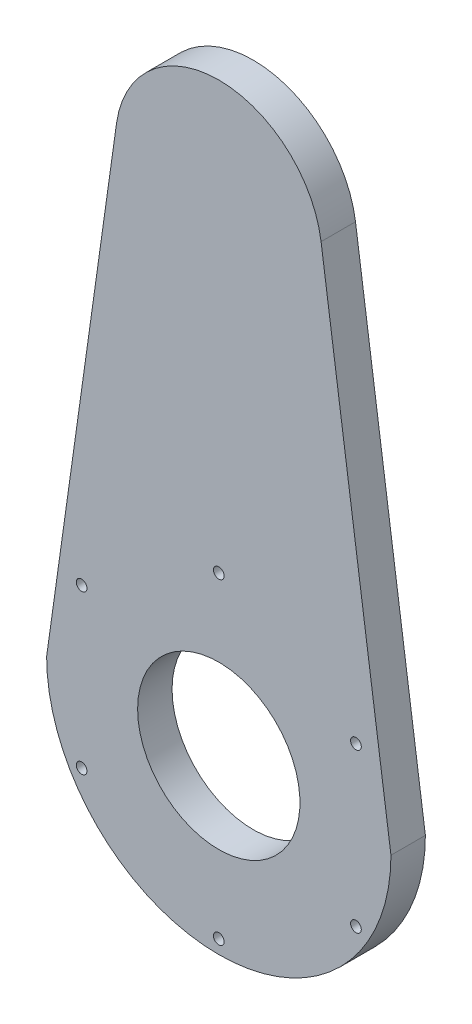
SolidWorks part; units mm, degrees
ref_plane "Ebene vorne" through (0, 0, 0) normal (0, 0, 1) x (1, 0, 0)
ref_plane "Ebene oben" through (0, 0, 0) normal (0, 1, 0) x (1, 0, 0)
ref_plane "Ebene rechts" through (0, 0, 0) normal (1, 0, 0) x (0, 0, -1)
sketch "Skizze1" plane through (0, 0, 0) normal (0, 0, 1) x (1, 0, 0)
  line L0 (0, 0) -> (-38225.0143, 0) construction
  line L1 (0, 0) -> (0, 38225.0143) construction
  line L2 (-50, 0) -> (-29.7072, 144.1811)
  line L3 (50, 0) -> (29.7072, 144.1811)
  arc A0 (-50, 0) -> (50, 0) centre (0, 0) ccw
  arc A1 (29.7072, 144.1811) -> (-29.7072, 144.1811) centre (0, 140) ccw
  point P13 (-30, 140)
  dimension "D1" = 60
  dimension "D2" = 100
  dimension "D3" = 140
extrude "Aufsatz-Linear austragen1" add sketch "Skizze1" along normal blind 10
sketch "Skizze2" plane through (0, 0, 0) normal (0, 0, -1) x (-1, 0, 0)
  circle A0 centre (0, 0) radius 23.575
  dimension "D1" = 47.15
extrude "Schnitt-Linear austragen1" cut sketch "Skizze2" against normal blind 10
hole_wizard "Ø3.1 (3.1) Durchmesser Bohrung1" positions "Skizze4" profile "Skizze5" hole size "Ø3.1" standard "ISO" end condition through all
sketch "Skizze4" plane through (0, 0, 0) normal (0, 0, -1) x (-1, 0, 0)
  line L0 (0, 0) -> (0, 50000) construction
  circle A0 centre (0, 0) radius 46 construction
  circle A1 centre (0, 0) radius 46 construction
  circle A2 centre (0, 0) radius 46 construction
  circle A3 centre (0, 0) radius 46 construction
  circle A4 centre (0, 0) radius 46 construction
  circle A5 centre (0, 0) radius 46 construction
  point P10 (0, 46)
  point P19 (39.8372, 23)
  point P21 (39.8372, -23)
  point P23 (0, -46)
  point P25 (-39.8372, -23)
  point P27 (-39.8372, 23)
  dimension "D1" = 92
  dimension "D2" = 6
sketch "Skizze5" plane through (39.8372, 23, 0) normal (1, 0, 0) x (0, 1, 0)
  line L0 (0, 0) -> (0, 10)
  line L1 (0, 10) -> (1.55, 10)
  line L2 (1.55, 10) -> (1.55, 0)
  line L5 (1.55, 0) -> (0, 0)
  line L11 (0, -6.35) -> (0, 107.95) construction
  dimension "Bohrerdurchmesser" = 3.1
  dimension "Bohrungstiefe" = 10
